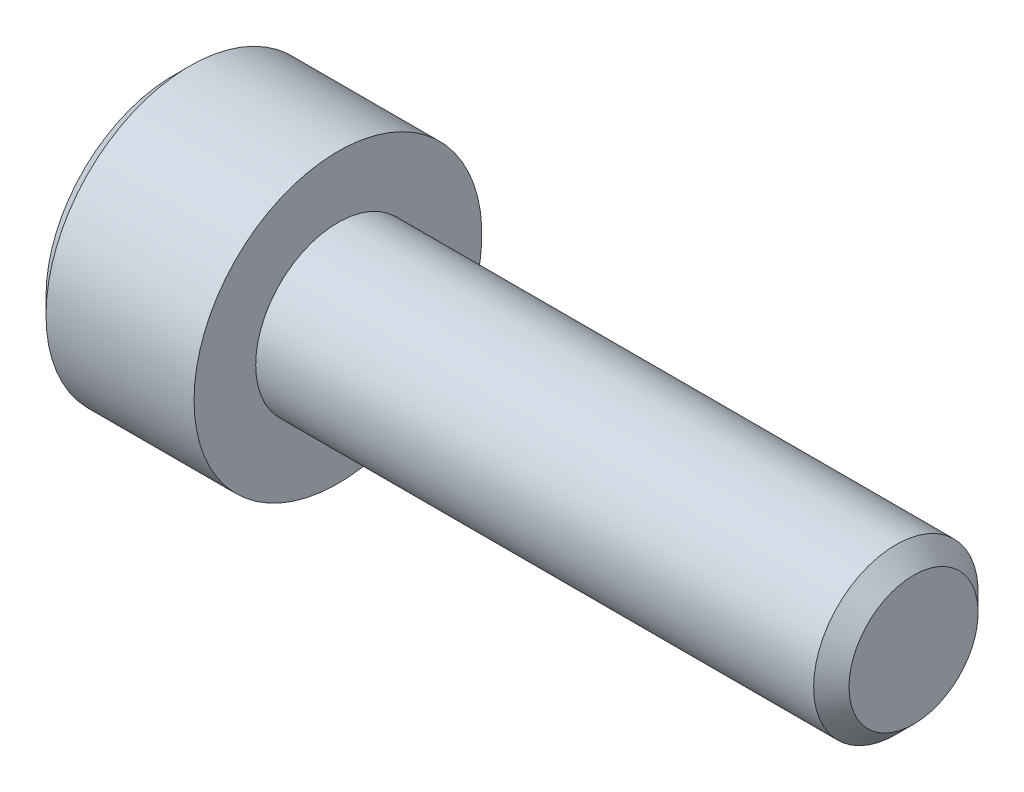
SolidWorks part; units mm, degrees
ref_plane "Front Plane" through (0, 0, 0) normal (0, 0, 1) x (1, 0, 0)
ref_plane "Top Plane" through (0, 0, 0) normal (0, 1, 0) x (1, 0, 0)
ref_plane "Right Plane" through (0, 0, 0) normal (1, 0, 0) x (0, 0, -1)
ref_plane "Plane1" through (1, 0, 0) normal (1, 0, 0) x (0, 0, -1)
ref_axis "Axis_X" through (-4.9, 0, 0) along (1, 0, 0)
ref_axis "Axis_Y" through (0, 3.85, 0) along (0, -1, 0)
ref_axis "Axis_Z" through (0, 0, -3.85) along (0, 0, 1)
sketch "Sketch1" plane through (0, 0, 0) normal (0, 0, 1) x (1, 0, 0)
  line L0 (-4, 0) -> (14, 0)
  line L1 (14, 0) -> (14, -1.5705)
  line L2 (14, -1.5705) -> (13.5705, -2)
  line L3 (13.5705, -2) -> (0, -2)
  line L4 (0, -2) -> (0, -3.5)
  line L5 (0, -3.5) -> (-3.6, -3.5)
  line L6 (-3.6, -3.5) -> (-4, -3.1)
  line L7 (-4, -3.1) -> (-4, 0)
  line L8 (0, 0) -> (-4, 0) construction
  line L9 (14, 1.5705) -> (13.5705, 2) construction
  line L10 (-4, 3.1) -> (-3.6, 3.5) construction
  point P16 (13.3, -2)
  dimension "A" = 7
  dimension "E" = 4
  dimension "MSM_1" = 3.141
  dimension "MSM_2" = 45
  dimension "MSM_3" = 0.4
  dimension "L" = 14
  dimension "Pitch_1" = 0.7
revolve "Revolve1" add sketch "Sketch1" angle 360 about axis through (-4.9, 0, 0) along (1, 0, 0)
sketch "Sketch2" plane through (-4, 0, 0) normal (-1, 0, 0) x (0, 0, 1)
  line L1 (0, 1.7321) -> (-1.5, 0.866)
  line L2 (-1.5, 0.866) -> (-1.5, -0.866)
  line L3 (-1.5, -0.866) -> (0, -1.7321)
  line L4 (0, -1.7321) -> (1.5, -0.866)
  line L5 (1.5, -0.866) -> (1.5, 0.866)
  line L6 (1.5, 0.866) -> (0, 1.7321)
  circle A0 centre (0, 0) radius 1.5 construction
  dimension "B" = 3
extrude "Cut-Extrude1" cut sketch "Sketch2" against normal blind 2
ref_plane "Dim. B_s" through (14, 0, 0) normal (1, 0, 0) x (0, 0, -1)
sketch "Sketch3" plane through (0, 0, 0) normal (0, 0, 1) x (1, 0, 0)
  line L0 (0, 0) -> (14, 0) construction
  line L1 (14, -1.3128) -> (14, 1.3128) construction
  line L3 (13.99, 2) -> (14, 2)
  line L5 (13.99, 2) -> (13.99, 1.99)
  line L6 (13.99, 1.99) -> (14, 1.99)
  line L7 (14, 2) -> (14, 1.99)
  line L8 (11, 2) -> (11.01, 2)
  line L9 (11, 2) -> (11, 1.99)
  line L10 (11, 1.99) -> (11.01, 1.99)
  line L11 (11.01, 2) -> (11.01, 1.99)
  dimension "MSM_5" = 0.01
  dimension "A_s" = 3
revolve "Cut-Revolve1" [suppressed] cut sketch "Sketch3" angle 360 about L0
equation "\"Factor\"= 1.082532"
equation "\"ATD_1\"= 4.134"
equation "\"L_s\"= 10"
equation "\"L_s\"= IIF ( ( \"M\" = 12 and \"L\" > 50 ) , 36 , IIF ( ( \"M\" = 10 and \"L\" > 40 ) , 32 , IIF ( ( \"M\" = 8 and \"L\" > 35 ) , 28 , IIF ( ( \"M\" = 6 and \"L\" > 30 ) , 24 , IIF ( ( \"M\" = 5 and \"L\" > 25 ) , 22 , IIF ( ( \"M\" = 4 and \"L\" > 25 ) , 20 , IIF ( ( \"M\" = 3 and \"L\" > 20 ) , 18 , \"L\" ) ) ) ) ) ) )"
equation "\"A\"= IIF ( \"M\" = 12 , 18 , IIF ( \"M\" = 10 , 16 , IIF ( \"M\" = 8 , 13 , IIF ( \"M\" = 6 , 10 , IIF ( \"M\" = 5 , 8.5 , IIF ( \"M\" = 4 , 7 , IIF ( \"M\" = 3 , 5.5 , IIF ( \"M\" = 2.6 or \"M\" = 2.5 , 4.5 , 3.8 ) ) ) ) ) ) ) )"
equation "\"E\"= \"M\""
equation "\"B\"= IIF ( \"M\" = 12 , 10 , IIF ( \"M\" = 10 , 8 , IIF ( \"M\" = 8 , 6 , IIF ( \"M\" = 6 , 5 , IIF ( \"M\" = 5 , 4 , IIF ( \"M\" = 4 , 3 , IIF ( \"M\" = 3 , 2.5 , IIF ( \"M\" = 2.6 or \"M\" = 2.5 , 2 , 1.5 ) ) ) ) ) ) ) )"
equation "\"MSM_4\"= \"M\" * 0.5"
equation "\"MSM_1\"= IIF ( \"M\" = 12 , 9.853 , IIF ( \"M\" = 10 , 8.16 , IIF ( \"M\" = 8 , 6.466 , IIF ( \"M\" = 6 , 4.773 , IIF ( \"M\" = 5 , 4.019 , IIF ( \"M\" = 4 , 3.141 , IIF ( \"M\" = 3 , 2.387 , IIF ( \"M\" = 2.6 , 2.048 , IIF ( \"M\" = 2.5 , 1.948 , 1.509 ) ) ) ) ) ) ) ) )"
equation "\"MSM_2\"= 45"
equation "\"MSM_3\"= IIF ( \"M\" = 2.6 , 0.26 , \"E\" * 0.1 )"
equation "\"Thread1\" = IIF ( ( ( \"M\" = 12 ) and ( \"L\" > 50 ) ) or ( ( \"M\" = 10 ) and ( \"L\" > 40 ) ) or ( ( \"M\" = 8 ) and ( \"L\" > 35 ) ) or ( ( \"M\" = 6 ) and ( \"L\" > 30 ) ) or ( ( \"M\" = 5 ) and ( \"L\" > 25 ) ) or ( ( \"M\" = 4 ) and ( \"L\" > 25 ) ) or ( \"M\" = 3 ) and ( \"L\" > 2 ) , \"suppressed\" , \"unsuppressed\" )"
equation "\"Thread2\" = IIF ( ( ( \"M\" = 12 ) and ( \"L\" > 50 ) ) or ( ( \"M\" = 10 ) and ( \"L\" > 40 ) ) or ( ( \"M\" = 8 ) and ( \"L\" > 35 ) ) or ( ( \"M\" = 6 ) and ( \"L\" > 30 ) ) or ( ( \"M\" = 5 ) and ( \"L\" > 25 ) ) or ( ( \"M\" = 4 ) and ( \"L\" > 25 ) ) or ( \"M\" = 3 ) and ( \"L\" > 2 ) , \"unsuppressed\" , \"suppressed\" )"
equation "\"MSM_5\"= 0.01"
equation "\"Cut-Revolve1\"= IIF ( \"TYP\" = 2 , \"unsuppressed\" , \"suppressed\" )"
equation "\"Pitch_1\"= IIF ( \"M\" = 12 , 1.75 , IIF ( \"M\" = 10 , 1.5 , IIF ( \"M\" = 8 , 1.25 , IIF ( \"M\" = 6 , 1 , IIF ( \"M\" = 5 , 0.8 , IIF ( \"M\" = 4 , 0.7 , IIF ( \"M\" = 3 , 0.5 , IIF ( \"M\" = 2.6 or \"M\" = 2.5 , 0.45 , 0.4 ) ) ) ) ) ) ) )"
equation "\"ATD_2\"= round ( \"M\" - \"Factor\" * \"Pitch_1\" , 3 )"
